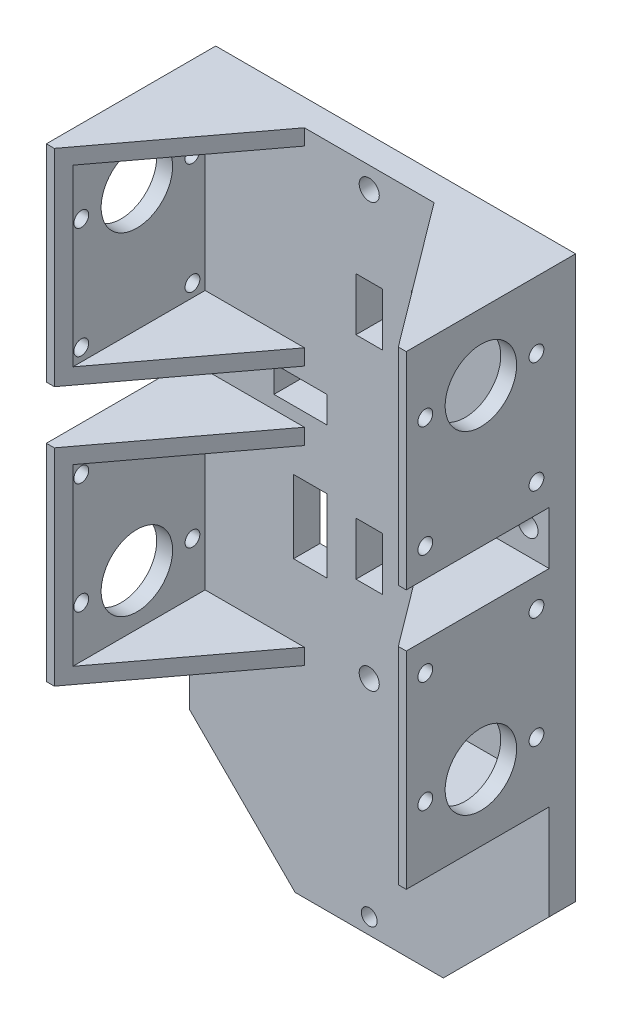
SolidWorks part; units mm, degrees
ref_plane "正面" through (0, 0, 0) normal (0, 0, 1) x (1, 0, 0)
ref_plane "平面" through (0, 0, 0) normal (0, 1, 0) x (1, 0, 0)
ref_plane "右側面" through (0, 0, 0) normal (1, 0, 0) x (0, 0, -1)
sketch "ｽｹｯﾁ5" plane through (0, 0, 0) normal (0, 1, 0) x (1, 0, 0)
  line L0 (-34, -32) -> (-34, 0)
  line L1 (-34, 0) -> (-10, 0)
  line L2 (-10, 0) -> (-34, -32)
  line L3 (-55, 0) -> (55, 0) construction
  dimension "D1" = 24
  dimension "D2" = 32
  dimension "D3" = 10
extrude "ﾎﾞｽ - 押し出し3" add sketch "ｽｹｯﾁ5" against normal blind 39 from offset 5 offset against normal yes
shell "ｼｪﾙ2" thickness 3 removed face at (-22, -24.5, 16)
sketch "ｽｹｯﾁ7" plane through (-31, 0, 0) normal (1, 0, 0) x (0, 0, -1)
  line L0 (-3, -41) -> (-3, -8) construction
  line L1 (-26.4, -31.4) -> (-5.4, -31.4) construction
  line L2 (-26.4, -31.4) -> (-26.4, -10.4) construction
  line L3 (-26.4, -10.4) -> (-5.4, -10.4) construction
  line L4 (-5.4, -31.4) -> (-5.4, -10.4) construction
  line L5 (-3, -8) -> (-28, -8) construction
  circle A0 centre (-15.9, -31.4) radius 6.75
  circle A1 centre (-26.4, -31.4) radius 1.4
  circle A2 centre (-5.4, -31.4) radius 1.4
  circle A3 centre (-5.4, -10.4) radius 1.4
  circle A4 centre (-26.4, -10.4) radius 1.4
  point P10 (-15.9, -31.4)
  dimension "D3" = 2.8
  dimension "D6" = 13.5
  dimension "D1" = 21
  dimension "D2" = 21
  dimension "D4" = 2.4
  dimension "D5" = 2.4
extrude "ｶｯﾄ - 押し出し5" cut sketch "ｽｹｯﾁ7" against normal through all
sketch "ｽｹｯﾁ1" plane through (0, 0, 0) normal (0, 0, 1) x (1, 0, 0)
  line L0 (-34, -44) -> (-34, -5) construction
  line L1 (34, -44) -> (-34, -44)
  line L2 (34, -44) -> (34, 44)
  line L3 (34, 44) -> (-34, 44)
  line L4 (-34, -44) -> (-34, 44)
  line L5 (34, -44) -> (-34, 44) construction
  line L6 (34, 44) -> (-34, -44) construction
  line L7 (-34, -44) -> (-10, -44) construction
  point P0 (0, 0)
  point P6 (0, 0)
  point P9 (0, 0)
  point P10 (0, 0)
extrude "ﾎﾞｽ - 押し出し1" add sketch "ｽｹｯﾁ1" along normal blind 3 and the other way blind 2 contours L4 L1 L2 L3
sketch "ｽｹｯﾁ8" plane through (0, 0, 0) normal (0, 0, 1) x (1, 0, 0)
  line L0 (-34, -44) -> (-34, -5) construction
  line L1 (-34, -5) -> (-22.8121, -5)
  line L2 (-34, -5) -> (-34, -44)
  line L3 (-34, -44) -> (-22.8121, -44)
  line L4 (-22.8121, -5) -> (-22.8121, -44)
  point P4 (0, 0)
  point P6 (0, 0)
  point P10 (0, 0)
extrude "ｶｯﾄ - 押し出し6" cut sketch "ｽｹｯﾁ8" against normal blind 2 from vertex starting at point (-34, -5, 32)
mirror "ﾐﾗｰ1" about plane through (0, 0, 0) normal (1, 0, 0) of bodies 136 101
mirror "ﾐﾗｰ2" about plane through (0, 0, 0) normal (0, 1, 0) of bodies 134
sketch "ｽｹｯﾁ9" plane through (0, 0, 3) normal (0, 0, 1) x (1, 0, 0)
  circle A0 centre (-30, 0) radius 1.9
  circle A1 centre (0, 40) radius 1.9
  circle A2 centre (30, 0) radius 1.9
  circle A3 centre (0, -40) radius 1.9
  point P8 (0, 0)
  point P10 (0, 0)
  point P11 (0, 0)
  point P12 (0, 0)
  point P15 (1.0731, 6.2059)
  dimension "D1" = 3.8
  dimension "D2" = 30
  dimension "D3" = 30
  dimension "D4" = 40
  dimension "D5" = 40
extrude "ｶｯﾄ - 押し出し7" cut sketch "ｽｹｯﾁ9" against normal blind 10
sketch "ｽｹｯﾁ10" plane through (0, 0, 3) normal (0, 0, 1) x (1, 0, 0)
  line L1 (2.5, -25) -> (-2.5, -25)
  line L2 (2.5, -25) -> (2.5, -15)
  line L3 (2.5, -15) -> (-2.5, -15)
  line L4 (-2.5, -25) -> (-2.5, -15)
  line L5 (2.5, -25) -> (-2.5, -15) construction
  line L6 (2.5, -15) -> (-2.5, -25) construction
  line L7 (2.5, 15) -> (-2.5, 15)
  line L8 (2.5, 15) -> (2.5, 25)
  line L9 (2.5, 25) -> (-2.5, 25)
  line L10 (-2.5, 15) -> (-2.5, 25)
  line L11 (2.5, 15) -> (-2.5, 25) construction
  line L12 (2.5, 25) -> (-2.5, 15) construction
  point P0 (0, -20)
  point P5 (0, 20)
  point P10 (0, 0)
  dimension "D1" = 5
  dimension "D2" = 10
  dimension "D3" = 20
  dimension "D4" = 20
extrude "ｶｯﾄ - 押し出し8" cut sketch "ｽｹｯﾁ10" against normal blind 10
sketch "ｽｹｯﾁ11" plane through (0, 0, 3) normal (0, 0, 1) x (1, 0, 0)
  line L0 (31, 38.15) -> (31, 24.65) construction
  line L1 (14.3, 13.75) -> (8, 13.75)
  line L2 (14.3, 13.75) -> (14.3, 27.55)
  line L3 (14.3, 27.55) -> (8, 27.55)
  line L4 (8, 13.75) -> (8, 27.55)
  line L5 (14.3, 13.75) -> (8, 27.55) construction
  line L6 (14.3, 27.55) -> (8, 13.75) construction
  line L7 (-8, -27.55) -> (-14.3, -27.55)
  line L8 (-8, -27.55) -> (-8, -13.75)
  line L9 (-8, -13.75) -> (-14.3, -13.75)
  line L10 (-14.3, -27.55) -> (-14.3, -13.75)
  line L11 (-8, -27.55) -> (-14.3, -13.75) construction
  line L12 (-8, -13.75) -> (-14.3, -27.55) construction
  line L13 (31, 38.15) -> (31, 24.65)
  line L15 (-31, -38.15) -> (-31, -24.65) construction
  line L16 (-31, -38.15) -> (-31, -24.65)
  point P0 (11.15, 20.65)
  point P5 (-11.15, -20.65)
  point P10 (18.6196, 23.8753)
  point P11 (0, 0)
  point P12 (0, 0)
  point P15 (31, 31.4)
  point P18 (0, 0)
  point P19 (-15.6088, -28.6429)
  point P20 (-31, -31.4)
  dimension "D1" = 6.3
  dimension "D2" = 3.85
  dimension "D3" = 17.65
  dimension "D4" = 23
  dimension "D5" = 3.85
  dimension "D6" = 23
extrude "ｶｯﾄ - 押し出し9" cut sketch "ｽｹｯﾁ11" against normal blind 10 contours L10 L7 L8 L9 | L4 L1 L2 L3 region at (11.15, 20.65, 3) region at (-11.15, -20.65, 3)
sketch "ｽｹｯﾁ12" plane through (0, 0, 3) normal (0, 0, 1) x (1, 0, 0)
  line L1 (-8, -2.5) -> (-18, -2.5)
  line L2 (-8, -2.5) -> (-8, 2.5)
  line L3 (-8, 2.5) -> (-18, 2.5)
  line L4 (-18, -2.5) -> (-18, 2.5)
  line L5 (-8, -2.5) -> (-18, 2.5) construction
  line L6 (-8, 2.5) -> (-18, -2.5) construction
  line L7 (18, -2.5) -> (8, -2.5)
  line L8 (18, -2.5) -> (18, 2.5)
  line L9 (18, 2.5) -> (8, 2.5)
  line L10 (8, -2.5) -> (8, 2.5)
  line L11 (18, -2.5) -> (8, 2.5) construction
  line L12 (18, 2.5) -> (8, -2.5) construction
  point P0 (-13, 0)
  point P5 (13, 0)
  point P10 (0, 0)
  point P12 (0, 0)
  dimension "D1" = 5
  dimension "D2" = 10
  dimension "D3" = 13
  dimension "D4" = 13
extrude "ｶｯﾄ - 押し出し10" cut sketch "ｽｹｯﾁ12" against normal blind 10
sketch "ｽｹｯﾁ13" plane through (0, -44, 0) normal (0, -1, 0) x (1, 0, 0)
  line L0 (34, -2) -> (34, 30) construction
  line L1 (-34, -2) -> (34, -2)
  line L2 (-34, -2) -> (-34, 3)
  line L3 (-34, 3) -> (34, 3)
  line L4 (34, -2) -> (34, 3)
  line L5 (12.25, 3) -> (-12.25, 3) construction
  point P7 (0, 0)
extrude "ﾎﾞｽ - 押し出し4" add sketch "ｽｹｯﾁ13" along normal blind 38
chamfer "面取り2" distance 20 angle 45 2 edges at (-34, -82, 0.5) (34, -82, 0.5)
sketch "ｽｹｯﾁ14" plane through (0, 0, -2) normal (0, 0, -1) x (-1, 0, 0)
  line L0 (14, -82) -> (-14, -82) construction
  line L1 (23.4, -79) -> (-23.4, -79) construction
  line L2 (23.4, -79) -> (23.4, -47.08) construction
  line L3 (23.4, -47.08) -> (-23.4, -47.08) construction
  line L4 (-23.4, -79) -> (-23.4, -47.08) construction
  line L5 (23.4, -79) -> (-23.4, -47.08) construction
  line L6 (23.4, -47.08) -> (-23.4, -79) construction
  circle A0 centre (-23.4, -47.08) radius 1.5
  circle A1 centre (23.4, -47.08) radius 1.5
  circle A2 centre (0, -79) radius 1.5
  point P0 (0, -63.04)
  point P9 (0, 0)
  point P12 (0, -82)
  dimension "D3" = 3
  dimension "D1" = 46.8
  dimension "D2" = 31.92
  dimension "D4" = 3
extrude "ｶｯﾄ - 押し出し11" cut sketch "ｽｹｯﾁ14" against normal blind 35
equation "\"D3@ｽｹｯﾁ9\"=\"D2@ｽｹｯﾁ9\""
equation "\"D5@ｽｹｯﾁ9\"=\"D4@ｽｹｯﾁ9\""
equation "\"D4@ｽｹｯﾁ10\"=\"D3@ｽｹｯﾁ10\""
equation "\"D4@ｽｹｯﾁ11\"=26-3"
equation "\"D6@ｽｹｯﾁ11\"=26-3"
equation "\"D4@ｽｹｯﾁ12\"=\"D3@ｽｹｯﾁ12\""
